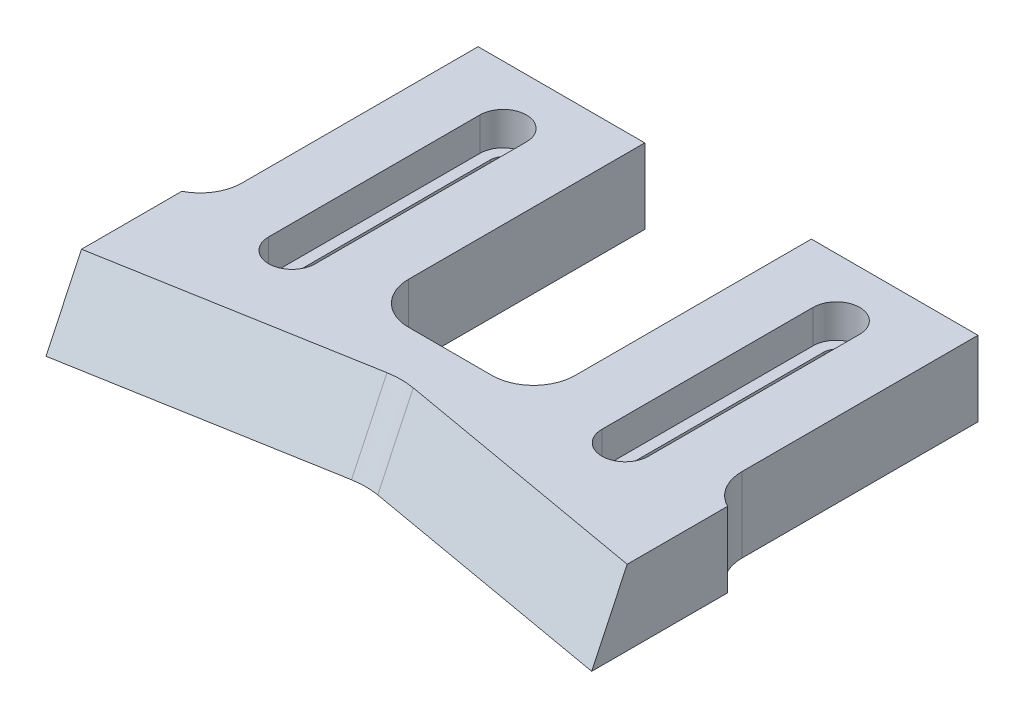
SolidWorks part; units mm, degrees
material "POM Acetal Copolymer"
ref_plane "Front Plane" through (0, 0, 0) normal (0, 0, 1) x (1, 0, 0)
ref_plane "Top Plane" through (0, 0, 0) normal (0, 1, 0) x (1, 0, 0)
ref_plane "Right Plane" through (0, 0, 0) normal (1, 0, 0) x (0, 0, -1)
sketch "Sketch1" plane through (0, 0, 0) normal (0, 1, 0) x (1, 0, 0)
  line L0 (0, 0) -> (0, 50)
  line L1 (0, 50) -> (75.5, 50)
  line L2 (75.5, 50) -> (75.5, 0)
  line L3 (75.5, 0) -> (37.75, 6.6563)
  line L4 (37.75, 6.6563) -> (0, 0)
  dimension "D1" = 50
  dimension "D2" = 80
  dimension "D3" = 75.5
extrude "Boss-Extrude1" add sketch "Sketch1" along normal blind 9
sketch "Sketch4" plane through (0, 9, 0) normal (0, 1, 0) x (1, 0, 0)
  line L0 (17.75, 43) -> (17.75, 17.6563) construction
  line L1 (19.25, 43) -> (19.25, 17.6563)
  line L2 (16.25, 43) -> (16.25, 17.6563)
  line L3 (57.75, 43) -> (57.75, 17.6563) construction
  line L4 (59.25, 43) -> (59.25, 17.6563)
  line L5 (56.25, 43) -> (56.25, 17.6563)
  line L9 (75.5, 50) -> (0, 50) construction
  arc A0 (19.25, 43) -> (16.25, 43) centre (17.75, 43) ccw
  arc A1 (16.25, 17.6563) -> (19.25, 17.6563) centre (17.75, 17.6563) ccw
  arc A2 (59.25, 43) -> (56.25, 43) centre (57.75, 43) ccw
  arc A3 (56.25, 17.6563) -> (59.25, 17.6563) centre (57.75, 17.6563) ccw
  point P2 (17.75, 30.3282)
  point P7 (57.75, 30.3282)
  dimension "D1" = 3
  dimension "D2" = 3
  dimension "D3" = 40
  dimension "D4" = 20
  dimension "D5" = 11
  dimension "D6" = 7
extrude "Cut-Extrude2" cut sketch "Sketch4" against normal up to next
sketch "Sketch5" plane through (0, 9, 0) normal (0, 1, 0) x (1, 0, 0)
  line L0 (75.5, 50) -> (0, 50) construction
  line L1 (27.75, 50) -> (47.75, 50)
  line L2 (27.75, 50) -> (27.75, 16.6563)
  line L3 (27.75, 16.6563) -> (47.75, 16.6563)
  line L4 (47.75, 50) -> (47.75, 16.6563)
  line L7 (67.75, 50) -> (75.5, 50)
  line L8 (0, 50) -> (7.75, 50)
  line L9 (0, 50) -> (0, 16.6563)
  line L10 (0, 16.6563) -> (7.75, 16.6563)
  line L11 (7.75, 50) -> (7.75, 16.6563)
  line L12 (67.75, 50) -> (67.75, 16.6563)
  line L13 (67.75, 16.6563) -> (75.5, 16.6563)
  line L14 (75.5, 50) -> (75.5, 16.6563)
  arc A0 (19.25, 43) -> (16.25, 43) centre (17.75, 43) ccw construction
  arc A1 (59.25, 43) -> (56.25, 43) centre (57.75, 43) ccw construction
  point P6 (17.75, 44.5)
  point P21 (57.75, 44.5)
  dimension "D1" = 20
  dimension "D2" = 20
  dimension "D3" = 10
  dimension "D4" = 10
  dimension "D5" = 10
extrude "Cut-Extrude3" cut sketch "Sketch5" against normal blind 10
fillet "Fillet1" radius 5 4 edges at (67.75, 4.5, -16.6563) (47.75, 4.5, -16.6563) (27.75, 4.5, -16.6563) (7.75, 4.5, -16.6563)
sketch "Sketch6" plane through (0, 9, 0) normal (0, 1, 0) x (1, 0, 0)
  line L0 (17.75, 43) -> (17.75, 17.6563) construction
  line L1 (20.55, 43) -> (20.55, 17.6563)
  line L2 (14.95, 43) -> (14.95, 17.6563)
  line L3 (57.75, 43) -> (57.75, 17.6563) construction
  line L4 (60.55, 43) -> (60.55, 17.6563)
  line L5 (54.95, 43) -> (54.95, 17.6563)
  arc A0 (20.55, 43) -> (14.95, 43) centre (17.75, 43) ccw
  arc A1 (14.95, 17.6563) -> (20.55, 17.6563) centre (17.75, 17.6563) ccw
  arc A2 (60.55, 43) -> (54.95, 43) centre (57.75, 43) ccw
  arc A3 (54.95, 17.6563) -> (60.55, 17.6563) centre (57.75, 17.6563) ccw
  point P4 (17.75, 30.3282)
  point P9 (57.75, 30.3282)
  dimension "D1" = 5.6
  dimension "D2" = 5.6
extrude "Cut-Extrude4" cut sketch "Sketch6" against normal blind 4
chamfer "Chamfer1" distance 9 angle 25 2 edges at (56.625, 9, -3.3282) (18.875, 9, -3.3282) first distance on face at (56.625, 4.5, -3.3282) first distance on face at (18.875, 4.5, -3.3282)
fillet "Fillet2" radius 10 1 edges at (37.75, 4.5, -8.7871)
sketch "Sketch7" plane through (0, 9, 0) normal (0, 1, 0) x (1, 0, 0)
  line L1 (0, 0) -> (5, 0)
  line L2 (0, 0) -> (0, 18.1208)
  line L3 (0, 18.1208) -> (5, 18.1208)
  line L4 (5, 0) -> (5, 18.1208)
  line L5 (75.5, 0) -> (70.5, 0)
  line L6 (75.5, 0) -> (75.5, 18.1208)
  line L7 (75.5, 18.1208) -> (70.5, 18.1208)
  line L8 (70.5, 0) -> (70.5, 18.1208)
  dimension "D1" = 5
extrude "Cut-Extrude5" cut sketch "Sketch7" against normal up to next
